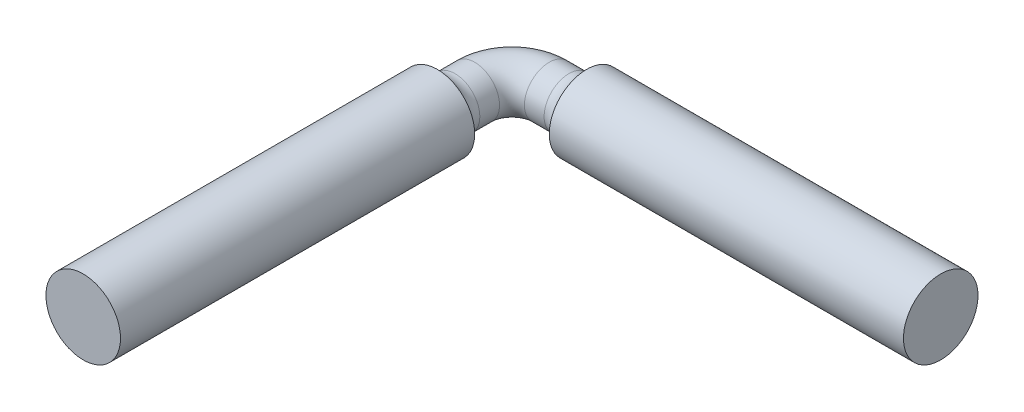
SolidWorks part; units mm, degrees
ref_plane "정면" through (0, 0, 0) normal (0, 0, 1) x (1, 0, 0)
ref_plane "윗면" through (0, 0, 0) normal (0, 1, 0) x (1, 0, 0)
ref_plane "우측면" through (0, 0, 0) normal (1, 0, 0) x (0, 0, -1)
sketch "스케치1" plane through (0, 0, 0) normal (0, 0, 1) x (1, 0, 0)
  circle A0 centre (0, 0) radius 2
  dimension "D1" = 4
sketch "스케치2" plane through (0, 0, 0) normal (0, 1, 0) x (1, 0, 0)
  line L0 (0, 0) -> (0, 31.5)
  line L1 (-2, 0) -> (2, 0) construction
  line L2 (3, 34.5) -> (34.5, 34.5)
  arc A0 (3, 34.5) -> (0, 31.5) centre (3, 31.5) ccw
sweep "스윕1" add profiles "스케치1" path "스케치2"
sketch "스케치3" plane through (0, 0, 0) normal (0, 0, 1) x (1, 0, 0)
  circle A0 centre (0, 0) radius 3
  dimension "D1" = 6
sketch "스케치4" plane through (34.5, 0, 0) normal (1, 0, 0) x (0, 0, -1)
  circle A0 centre (34.5, 0) radius 3
  dimension "D1" = 6
extrude "보스-돌출1" add sketch "스케치3" against normal blind 28.5 contours A0
extrude "보스-돌출2" add sketch "스케치4" against normal blind 28.5 contours A0
fillet "필렛1" radius 1.5 2 edges at (2, 0, -28.5) (6, 0, -36.5)
